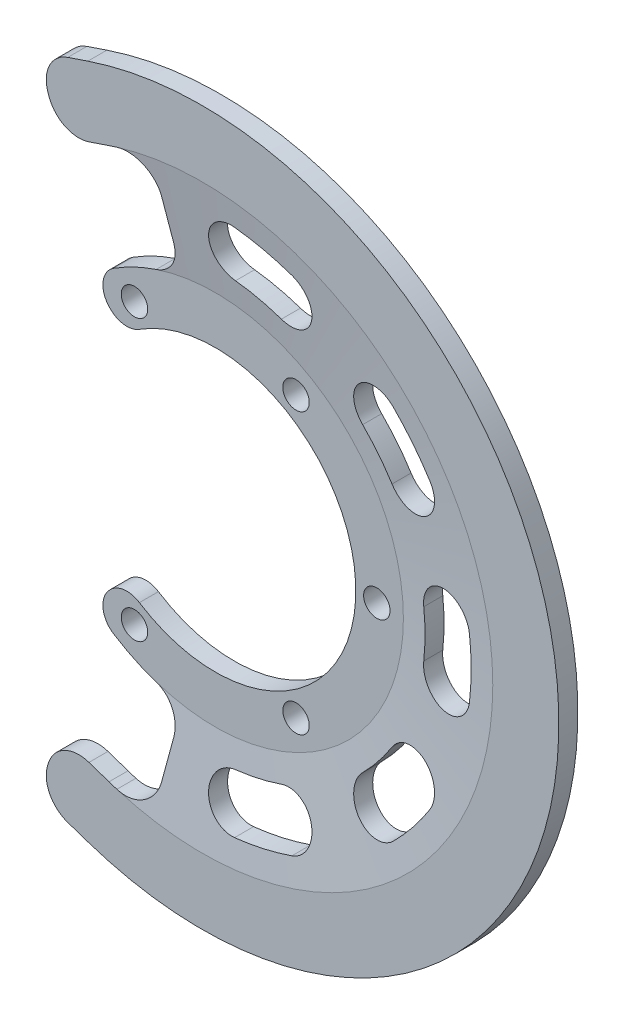
SolidWorks part; units mm, degrees
note: The reader was unsure of these and kept them because the rebuilt part matched: shared geometry of "Sketch1<3>", "Sketch2<3>", "Sketch1<5>".
material "AISI 304"
ref_plane "Front Plane" through (0, 0, 0) normal (0, 0, 1) x (1, 0, 0)
ref_plane "Top Plane" through (0, 0, 0) normal (0, 1, 0) x (1, 0, 0)
ref_plane "Right Plane" through (0, 0, 0) normal (1, 0, 0) x (0, 0, -1)
sketch "Sketch1" plane through (0, 0, 0) normal (0, 0, 1) x (1, 0, 0)
  line L0 (0, 0) -> (0, 33.77) construction
  line L1 (-29.5516, 34.2015) -> (-22.0787, 25.5528)
  line L2 (-22.0787, -25.5528) -> (-29.5516, -34.2015)
  line L3 (-27.432, 81.2174) -> (-39.4642, 77.1534)
  line L4 (-22.352, 66.1771) -> (-34.3842, 62.1131)
  line L5 (-39.4642, 77.1534) -> (-34.3842, 62.1131)
  line L6 (0, 0) -> (-158.75, 0) construction
  line L7 (-24.384, 72.1932) -> (-166.878, 24.0644) construction
  line L8 (0, 0) -> (85.725, 0) construction
  line L9 (-22.352, -66.1771) -> (-34.3842, -62.1131)
  line L10 (-39.4642, -77.1534) -> (-34.3842, -62.1131)
  line L11 (-27.432, -81.2174) -> (-39.4642, -77.1534)
  line L12 (-29.5516, 34.2015) -> (-34.3842, 62.1131)
  line L13 (-29.5516, -34.2015) -> (-34.3842, -62.1131)
  line L14 (0, 45.2) -> (0, 69.85) construction
  arc A0 (-25.4, 29.3967) -> (-25.4, -29.3967) centre (0, 0) cw
  arc A1 (-22.0787, 25.5528) -> (-22.0787, -25.5528) centre (0, 0) cw
  arc A2 (-29.5516, 34.2015) -> (-29.5516, -34.2015) centre (0, 0) cw
  arc A3 (-24.384, 72.1932) -> (76.2, 0) centre (0, 0) cw construction
  arc A4 (-22.352, 66.1771) -> (-22.352, -66.1771) centre (0, 0) cw
  arc A5 (-27.432, 81.2174) -> (-27.432, -81.2174) centre (0, 0) cw
  arc A6 (-24.384, 72.1932) -> (-36.195, -67.0549) centre (0, 0) cw construction
  circle A7 centre (-158.75, 0) radius 25.4 construction
  arc A8 (-27.432, 81.2174) -> (-40.7194, -75.4368) centre (0, 0) cw construction
  arc A9 (-22.352, 66.1771) -> (-33.1788, -61.467) centre (0, 0) cw construction
  arc A10 (6.3403, 57.1745) -> (18.7313, 54.3899) centre (0, 0) cw construction
  arc A11 (20.799, 60.3939) -> (7.0402, 63.4858) centre (0, 0) ccw
  arc A12 (16.6636, 48.386) -> (5.6404, 50.8632) centre (0, 0) ccw
  arc A13 (16.6636, 48.386) -> (20.799, 60.3939) centre (18.7313, 54.3899) ccw
  arc A14 (7.0402, 63.4858) -> (5.6404, 50.8632) centre (6.3403, 57.1745) ccw
  arc A19 (6.3403, 57.1745) -> (12.6129, 56.1252) centre (0, 0) cw construction
  arc A20 (43.2421, 27.3678) -> (36.1831, 36.1893) centre (0, 0) ccw
  arc A21 (43.2421, 27.3678) -> (53.9734, 34.1597) centre (48.6078, 30.7638) ccw
  arc A22 (45.1626, 45.1703) -> (36.1831, 36.1893) centre (40.6729, 40.6798) ccw
  arc A23 (53.9734, 34.1597) -> (45.1626, 45.1703) centre (0, 0) ccw
  arc A24 (40.6729, 40.6798) -> (48.6078, 30.7638) centre (0, 0) cw construction
  arc A25 (50.8623, -5.649) -> (50.8623, 5.649) centre (0, 0) ccw
  arc A26 (50.8623, -5.649) -> (63.4846, -7.051) centre (57.1735, -6.35) ccw
  arc A27 (63.4846, 7.051) -> (50.8623, 5.649) centre (57.1735, 6.35) ccw
  arc A28 (63.4846, -7.051) -> (63.4846, 7.051) centre (0, 0) ccw
  arc A29 (57.1735, 6.35) -> (57.1735, -6.35) centre (0, 0) cw construction
  arc A30 (36.1831, -36.1893) -> (43.2421, -27.3678) centre (0, 0) ccw
  arc A31 (36.1831, -36.1893) -> (45.1626, -45.1703) centre (40.6729, -40.6798) ccw
  arc A32 (53.9734, -34.1597) -> (43.2421, -27.3678) centre (48.6078, -30.7638) ccw
  arc A33 (45.1626, -45.1703) -> (53.9734, -34.1597) centre (0, 0) ccw
  arc A34 (48.6078, -30.7638) -> (40.6729, -40.6798) centre (0, 0) cw construction
  arc A35 (5.6404, -50.8632) -> (16.6636, -48.386) centre (0, 0) ccw
  arc A36 (5.6404, -50.8632) -> (7.0402, -63.4858) centre (6.3403, -57.1745) ccw
  arc A37 (20.799, -60.3939) -> (16.6636, -48.386) centre (18.7313, -54.3899) ccw
  arc A38 (7.0402, -63.4858) -> (20.799, -60.3939) centre (0, 0) ccw
  arc A39 (18.7313, -54.3899) -> (6.3403, -57.1745) centre (0, 0) cw construction
  circle A40 centre (0, 0) radius 57.525 construction
  point P6 (0, 57.525)
  point P28 (12.6129, 56.1252)
  point P40 (0, 0)
  point P41 (13.4181, 55.9382)
  point P46 (0, 0)
  point P47 (20.7909, 53.6364)
  point P50 (44.9148, 35.9414)
  point P57 (57.525, 0)
  point P64 (44.9148, -35.9414)
  point P66 (0, 0)
  point P72 (0, 0)
  point P78 (12.6129, -56.1252)
  dimension "D1" = 38.85
  dimension "D7" = 9.525
  dimension "D5" = 76.2
  dimension "D9" = 158.75
  dimension "D10" = 50.8
  dimension "D12" = 12.7
  dimension "D8" = 12.7
  dimension "D13" = 5
  dimension "D2" = 25.4
  dimension "D6" = 6.35
  dimension "D11" = 12.7
  dimension "D3" = 5.08
  dimension "D4" = 6.35
extrude "Boss-Extrude1" add sketch "Sketch1" along normal blind 4.572 contours A2 L1 A0 L2 | L1 A1 L2 A0
extrude "Boss-Extrude2" add sketch "Sketch1<3>" along normal blind 4.572 from offset 3.175 separate body contours A5 L3 L5 L4 A4 L9 L10 L11
sketch "Sketch1<3>" plane through (0, 0, 0) normal (0, 0, 1) x (1, 0, 0) same geometry as "Sketch1"
sketch "Sketch2" plane through (0, 0, 0) normal (1, 0, 0) x (0, 0, -1)
  line L0 (0, 45.2) -> (-4.572, 45.2)
  line L1 (-4.572, 45.2) -> (-7.747, 69.85)
  line L2 (-7.747, 69.85) -> (-3.175, 69.85)
  line L3 (-3.175, 69.85) -> (0, 45.2)
  line L4 (-3.175, -85.725) -> (-3.175, 85.725) construction
  line L5 (-3.175, -85.725) -> (-3.175, 85.725) construction
  line L6 (-3.175, -69.85) -> (-3.175, 69.85) construction
  line L7 (-3.175, -69.85) -> (-3.175, 69.85)
  line L8 (0, 0) -> (-46.4727, 0) construction
  line L9 (0, 25.4) -> (0, -25.4) construction
  line L10 (-7.747, 69.85) -> (-7.747, -69.85) construction
  line L11 (-7.747, 69.85) -> (-7.747, -69.85)
  point P4 (0, 0)
  point P16 (-8.4905, 69.85)
  point P17 (-7.4707, 69.85)
revolve "Revolve1" add sketch "Sketch2" angle 190 about L8
revolve "Revolve2" add sketch "Sketch2<3>" angle 10 about L8
sketch "Sketch2<3>" plane through (0, 0, 0) normal (1, 0, 0) x (0, 0, -1) same geometry as "Sketch2"
sketch "Sketch4" plane through (0, 0, 0) normal (0, 0, 1) x (1, 0, 0)
  circle A0 centre (0, 0) radius 38.8119 construction
  circle A1 centre (38.8119, 0) radius 3.175
  circle A2 centre (19.406, -33.6121) radius 3.175
  circle A3 centre (-19.406, -33.6121) radius 3.175
  circle A5 centre (-19.406, 33.6121) radius 3.175
  circle A6 centre (19.406, 33.6121) radius 3.175
  circle A7 centre (-38.8119, 0) radius 3.175 [skipped]
  point P5 (4.5306, 26.2836)
  point P6 (0, 0)
  point P18 (0, 0)
  dimension "D1" = 77.6238
  dimension "D2" = 6.35
  dimension "D3" = 6
fillet "Fillet1" radius 5.588 4 edges at (-29.5516, -34.2015, 2.286) (-22.0787, -25.5528, 2.286) (-22.0787, 25.5528, 2.286) (-29.5516, 34.2015, 2.286)
extrude "Cut-Extrude3" cut sketch "Sketch4" along direction (0, 0, 1) on the side against the normal through all and the other way through all
fillet "Fillet2" radius 7.62 8 edges at (-34.3842, -62.1131, 5.461) (-39.4642, -77.1534, 5.461) (-34.3842, 62.1131, 5.461) (-39.4642, 77.1534, 5.461) (-7.8489, -44.5133, 2.286) (-7.8489, 44.5133, 2.286) (-12.1293, 68.7888, 5.461) (-12.1293, -68.7888, 5.461)
extrude "Cut-Extrude6" cut sketch "Sketch1<5>" along normal through all contours A11 A14 A12 A13 | A21 A23 A22 A20 | A26 A28 A27 A25 | A31 A33 A32 A30 | A38 A37 A35 A36
sketch "Sketch1<5>" plane through (0, 0, 0) normal (0, 0, 1) x (1, 0, 0) same geometry as "Sketch1"
